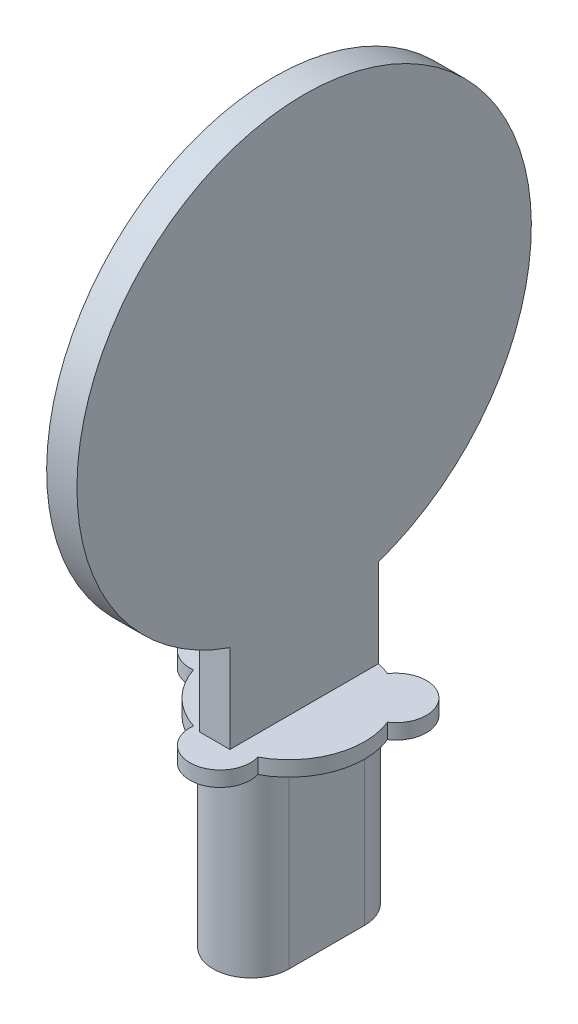
SolidWorks part; units mm, degrees
ref_plane "Front Plane" through (0, 0, 0) normal (0, 0, 1) x (1, 0, 0)
ref_plane "Top Plane" through (0, 0, 0) normal (0, 1, 0) x (1, 0, 0)
ref_plane "Right Plane" through (0, 0, 0) normal (1, 0, 0) x (0, 0, -1)
sketch "Sketch1" plane through (0, 0, 0) normal (0, 1, 0) x (1, 0, 0)
  line L0 (0, 2.5) -> (0, -2.5) construction
  line L1 (2.5, 2.5) -> (2.5, -2.5)
  line L2 (-2.5, 2.5) -> (-2.5, -2.5)
  line L3 (0.4358, -4.981) -> (-4.981, 0.4358) construction
  line L5 (-1, -4.899) -> (1, -4.899)
  line L6 (-1, -4.899) -> (-1, 4.899)
  line L7 (-1, 4.899) -> (1, 4.899)
  line L8 (1, -4.899) -> (1, 4.899)
  line L9 (-1, -4.899) -> (1, 4.899) construction
  line L10 (-1, 4.899) -> (1, -4.899) construction
  arc A1 (2.5, 2.5) -> (-2.5, 2.5) centre (0, 2.5) ccw
  arc A2 (-2.5, -2.5) -> (2.5, -2.5) centre (0, -2.5) ccw
  circle A3 centre (3.5355, 3.5355) radius 2
  circle A4 centre (-4.981, 0.4358) radius 2
  circle A5 centre (0.4358, -4.981) radius 2
  circle A6 centre (0, 0) radius 5
  point P3 (0, 0)
  point P9 (0, 5)
  point P10 (0, -5)
  point P18 (-2.2726, -2.2726)
  dimension "D3" = 2.5
  dimension "D4" = 4
  dimension "D5" = 4
  dimension "D6" = 4
  dimension "D7" = 10
  dimension "D2" = 10
  dimension "D9" = 2
  dimension "D1" = 25
  dimension "D8" = 90
  dimension "key_angle_offset" = 45
extrude "Boss-Extrude1" add sketch "Sketch1" against normal blind 13 contours L2 A2 L1 A1
extrude "Boss-Extrude2" add sketch "Sketch1<3>" against normal blind 1 contours A6 A5 | A6 A4 | A6 A3 | A6 region at (4.0819, 0, -4.0819) region at (0.5031, 0, 5.7507) region at (-5.7507, 0, -0.5031)
sketch "Sketch1<3>" plane through (0, 0, 0) normal (0, 1, 0) x (1, 0, 0) same geometry as "Sketch1"
extrude "Boss-Extrude3" add sketch "Sketch1<5>" along normal blind 20 contours L6 L7 L8 L5
sketch "Sketch1<5>" plane through (0, 0, 0) normal (0, 1, 0) x (1, 0, 0) same geometry as "Sketch1"
sketch "Sketch2" plane through (-1, 0, 0) normal (-1, 0, 0) x (0, 0, 1)
  line L0 (4.899, 20) -> (-4.899, 20) construction
  circle A0 centre (0, 20) radius 15
  dimension "D1" = 30
extrude "Boss-Extrude4" add sketch "Sketch2" against normal blind 2
equation "\"key_pin_length\"= 25.00mm"
equation "\"key_pin_dia\"= 20.00mm"
equation "\"driver_pin_travel\"= 3.00mm"
equation "\"driver_pin_dia\"= 0.3mm"
equation "\"driver_pin_neck_dia\"= 2.00mm"
equation "\"driver_pin_head_dia\" = 2mm"
equation "\"driver_pin_head_length\" = 2mm"
equation "\"plug_wall_thickness\" = 2mm"
equation "\"plug_spring_solid_length\"= 2mm"
equation "\"plug_length\"= 2 * \"key_pin_length\" + 2 * \"plug_wall_thickness\" + \"plug_spring_solid_length\""
equation "\"plug_dia\"= \"key_pin_dia\" + 2*(\"driver_pin_travel\" + 1mm + \"plug_spring_solid_length\" + 1mm)"
equation "\"true_gate_depth\" = 1.25mm"
equation "\"key_notches_dia\" = 4mm"
equation "\"D4@Sketch1\"=\"key_notches_dia\""
equation "\"D6@Sketch1\"=\"key_notches_dia\""
equation "\"D5@Sketch1\"=\"key_notches_dia\""
equation "\"key_notches_offset_angle\" = 25deg"
equation "\"D1@Sketch1\"=\"key_notches_offset_angle\""
